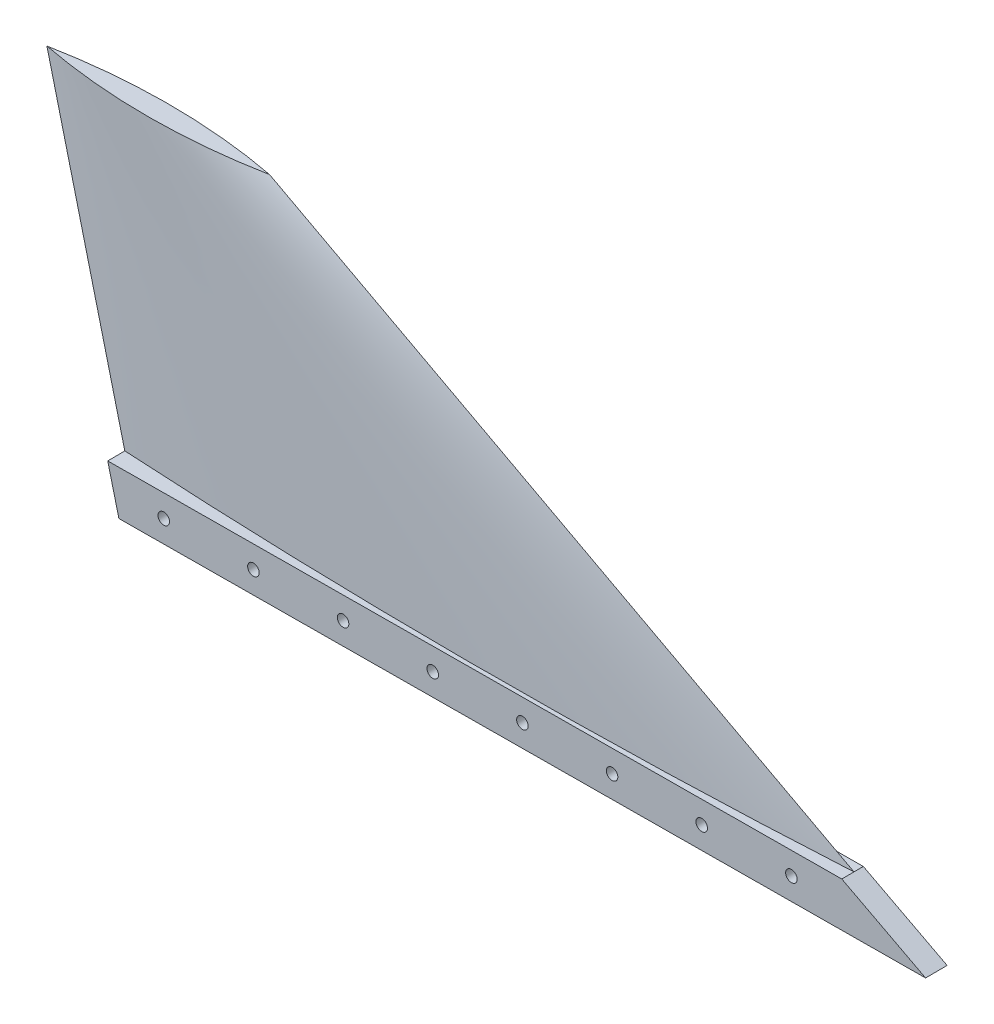
SolidWorks part; units mm, degrees
material "Aluminum Bronze"
ref_plane "Front Plane" through (0, 0, 0) normal (0, 0, 1) x (1, 0, 0)
ref_plane "Top Plane" through (0, 0, 0) normal (0, 1, 0) x (1, 0, 0)
ref_plane "Right Plane" through (0, 0, 0) normal (1, 0, 0) x (0, 0, -1)
sketch "Sketch1" plane through (0, 0, 0) normal (0, 1, 0) x (1, 0, 0)
  line L0 (0, 0) -> (457.2, 0) construction
  line L1 (228.6, 6.0452) -> (228.6, 0) construction
  arc A0 (0, 0) -> (457.2, 0) centre (228.6, -4319.2463) cw
  arc A1 (0, 0) -> (457.2, 0) centre (228.6, 4319.2463) ccw
  dimension "D1" = 457.2
  dimension "D2" = 6.0452
ref_plane "Plane2" through (0, 203.2, 0) normal (0, 1, 0) x (1, 0, 0)
sketch "Sketch5" plane through (0, 203.2, 0) normal (0, 1, 0) x (1, 0, 0)
  line L0 (0, 0) -> (76.2, 0) construction
  line L1 (0, 0) -> (-50.8, 0) construction
  line L2 (12.7, 6.0452) -> (12.7, 0) construction
  arc A0 (-50.8, 0) -> (76.2, 0) centre (12.7, -330.4858) cw
  arc A1 (-50.8, 0) -> (76.2, 0) centre (12.7, 330.4858) ccw
  dimension "D2" = 50.8
  dimension "D3" = 6.0452
  dimension "D1" = 127
loft "Loft4" add profiles "Sketch5", "Sketch1" connector at (-50.8, 203.2, 0) connector at (0, 0, 0)
ref_axis "Axis3" through (228.6, 254.2969, 0) along (0, -1, 0)
ref_axis "Axis1" through (76.2, 203.2, 0) along (-1, 0, 0)
ref_axis "Axis2" through (457.2, 0, 0) along (-1, 0, 0)
ref_plane "Plane3" through (0.0106, 0, 1.556) normal (0.0068, 0, 1) x (0, -1, 0)
ref_plane "Plane8" through (-0.0175, 0, -2.569) normal (0.0068, 0, 1) x (0, -1, 0)
sketch "Sketch10" plane through (-0.0175, 0, -2.569) normal (0.0068, 0, 1) x (0, -1, 0)
  line L0 (0, 457.1894) -> (0, 0)
  line L1 (0, 0) -> (-25.4, -6.3499)
  line L2 (0, 0) -> (-203.2, -50.7988) construction
  line L3 (-25.4, -6.3499) -> (-25.4, 409.5655)
  line L4 (-203.2, 76.1982) -> (0, 457.1894) construction
  line L5 (-25.4, 409.5655) -> (0, 457.1894)
  dimension "D1" = 25.4
extrude "Boss-Extrude1" add sketch "Sketch10" along normal blind 12.3444
ref_plane "Plane5" through (0, 0, 0) normal (-1, 0, 0.0068) x (-0.0068, 0, -1)
sketch "Sketch12" plane through (0, 0, 0) normal (-1, 0, 0.0068) x (0.0068, 0, 1)
  line L2 (16.1254, 0) -> (16.1254, 25.4)
  line L4 (-8.919, 0) -> (-8.919, 25.4)
  line L5 (16.1254, 25.4) -> (9.7754, 25.4)
  line L6 (16.1254, 25.4) -> (16.1254, 0)
  line L7 (16.1254, 0) -> (9.7754, 0)
  line L8 (9.7754, 25.4) -> (9.7754, 0)
  line L9 (-8.919, 25.4) -> (-2.569, 25.4)
  line L10 (-8.919, 25.4) -> (-8.919, 0)
  line L11 (-8.919, 0) -> (-2.569, 0)
  line L12 (-2.569, 25.4) -> (-2.569, 0)
  line L14 (9.7754, 0) -> (-2.569, 0) construction
  dimension "D1" = 6.35
extrude "Cut-Extrude1" cut sketch "Sketch12" against normal through all both and the other way through all contours L5 L8 L7 L2 | L12 L9 L4 L11 region at (0.0881, 12.7, 12.9501) region at (-0.0391, 12.7, -5.7439)
ref_plane "Plane4" through (0.097, 0, 14.2557) normal (0.0068, 0, 1) x (0, -1, 0)
hole_wizard "1/4 Clearance Hole1" positions "Sketch8" profile "Sketch9" hole size "1/4" standard "ANSI Inch" end condition through all
sketch "Sketch8" plane through (0.097, 0, 14.2557) normal (0.0068, 0, 1) x (0, -1, 0)
  point P0 (-12.7, 25.4)
  dimension "D1" = 12.7
  dimension "D2" = 25.4
sketch "Sketch9" plane through (25.4964, 12.7, 14.0828) normal (0, 1, 0) x (1, 0, -0.0068)
  line L0 (0, 0) -> (0, 20.6488)
  line L1 (0, 20.6488) -> (3.2639, 20.6488)
  line L2 (3.2639, 20.6488) -> (3.2639, 0)
  line L5 (3.2639, 0) -> (0, 0)
  line L11 (0, -6.35) -> (0, 107.95) construction
  dimension "Thru Hole Dia." = 6.5278
  dimension "Thru Hole Depth" = 20.6488
pattern_linear "LPattern1" count 8 spacing 50.8 along (1, 0, 0) of "1/4 Clearance Hole1"
sketch "Sketch13" [suppressed] plane through (0, 0, 0) normal (0, -1, 0) x (1, 0, 0)
  line L0 (3.8884, 5.2873) -> (445.7919, 2.2793) construction
  line L1 (0.0362, 5.3135) -> (457.215, 2.2016) construction
  line L2 (-3.917, -2.5424) -> (450.1427, -5.6332) construction
  line L3 (-0.0175, -2.569) -> (457.1613, -5.6809) construction
  spline S0 degree 3 poles (-6.35, 0) (62.9148, 2.5382) (132.2636, 3.81) (214.4874, 3.81) (227.3622, 3.7662) (240.2365, 3.6785) knots 0.407173 0.407173 0.407173 0.407173 0.907173 0.907173 1 1 1 1 construction
  spline S1 degree 3 poles (227.5601, -3.7507) (218.911, -3.7902) (175.8551, -3.8887) (132.7993, -3.497) (98.403, -2.8715) knots 0.251931 0.251931 0.251931 0.251931 0.314292 0.562361 0.562361 0.562361 0.562361 construction
sketch "Sketch14" plane through (0.0665, 0, 9.7751) normal (0.0068, 0, 1) x (1, 0, -0.0068)
  line L0 (0, 0) -> (457.1894, 0) construction
  line L1 (-0.019, 0.0762) -> (457.1894, 0.0762)
  line L2 (-0.019, 0.0762) -> (-0.019, -25.3238)
  line L3 (-0.019, -25.3238) -> (457.1894, -25.3238)
  line L4 (457.1894, 0.0762) -> (457.1894, -25.3238)
  line L5 (-6.3499, 25.4) -> (0, 0) construction
  dimension "D1" = 0.0762
  dimension "D2" = 25.4
extrude "Cut-Extrude2" cut sketch "Sketch14" against normal through all
equation "\"thick\"= 0.476"
equation "\"D3@Sketch5\"=\"thick\"/2"
equation "\"D2@Sketch1\"=\"thick\"/2"
equation "\"D1@Boss-Extrude1\"=\"thick\"+0.01"
